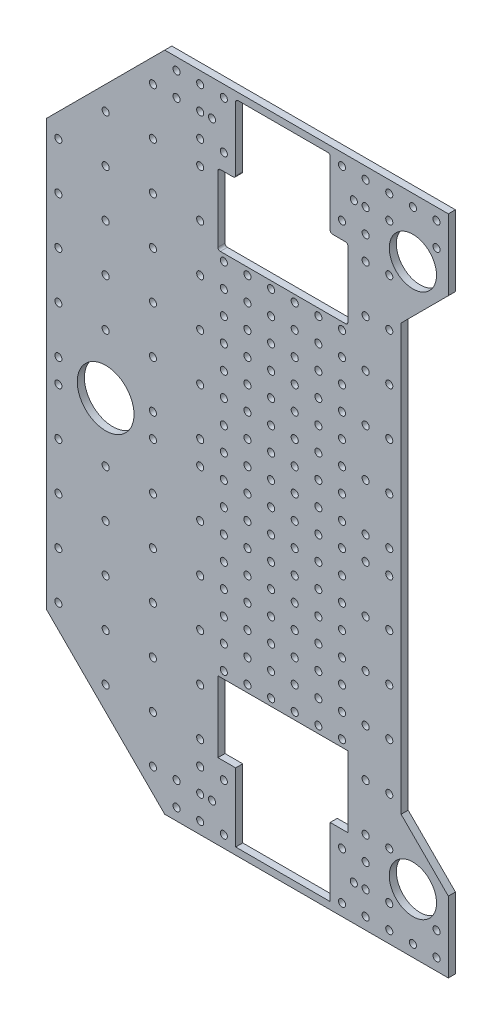
SolidWorks part; units mm, degrees
ref_plane "Front Plane" through (0, 0, 0) normal (0, 0, 1) x (1, 0, 0)
ref_plane "Top Plane" through (0, 0, 0) normal (0, 1, 0) x (1, 0, 0)
ref_plane "Right Plane" through (0, 0, 0) normal (1, 0, 0) x (0, 0, -1)
ref_axis "Axis1" through (-88.99, 0, 0) along (1, 0, 0)
ref_axis "Axis3" through (0, -55, 0) along (0, 1, 0)
sketch "Sketch1" plane through (0, 0, 0) normal (0, 0, 1) x (1, 0, 0)
  line L0 (-110, 90) -> (-110, -90)
  line L1 (-110, -90) -> (-60, -140)
  line L2 (-60, -140) -> (60, -140)
  line L3 (60, -140) -> (60, -110)
  line L4 (60, -110) -> (40, -90)
  line L5 (40, -90) -> (40, 90)
  line L6 (40, 90) -> (60, 110)
  line L7 (60, 110) -> (60, 140)
  line L8 (60, 140) -> (-60, 140)
  line L9 (-60, 140) -> (-110, 90)
  line L10 (-88.99, 0) -> (88.99, 0) construction
  circle A0 centre (78, 0) radius 38 construction
  circle A1 centre (78, -76) radius 38 construction
  circle A2 centre (78, 76) radius 38 construction
  point P2 (-110, 0)
  point P14 (-41.3479, 0)
  point P21 (0, 140)
  dimension "D15" = 76
  dimension "D1" = 180
  dimension "D2" = 170
  dimension "D3" = 50
  dimension "D4" = 50
  dimension "D5" = 135
  dimension "D6" = 110
  dimension "D7" = 20
  dimension "D8" = 180
  dimension "D9" = 120
  dimension "D10" = 28.2843
  dimension "D11" = 70.7107
  dimension "D12" = 50
  dimension "D13" = 30
  dimension "D14" = 30
  dimension "D16" = 120
  dimension "D17" = 280
extrude "Main" add sketch "Sketch1" along normal blind 3
sketch "Sketch2" plane through (0, 0, 3) normal (0, 0, 1) x (1, 0, 0)
  line L0 (-37.5, 108) -> (-37.5, 78)
  line L1 (-37.5, 78) -> (17.5, 78)
  line L2 (17.5, 78) -> (17.5, 108)
  line L3 (17.5, 108) -> (10, 108)
  line L4 (10, 108) -> (10, 137)
  line L5 (10, 137) -> (-30, 137)
  line L6 (-30, 137) -> (-30, 108)
  line L7 (-30, 108) -> (-37.5, 108)
  line L8 (0, -55) -> (0, 55) construction
  line L9 (-88.99, 0) -> (88.99, 0) construction
  line L10 (60, 140) -> (-60, 140) construction
  point P9 (-10, 78)
  dimension "D1" = 55
  dimension "D2" = 78
  dimension "D3" = 40
  dimension "D4" = 29
  dimension "D5" = 30
  dimension "D6" = 3
  dimension "D7" = 10
extrude "MotorCoderLeftHole" cut sketch "Sketch2" against normal through all
fillet "Fillet1" radius 1 8 edges at (-30, 137, 1.5) (10, 108, 1.5) (17.5, 108, 1.5) (10, 137, 1.5) (17.5, 78, 1.5) (-37.5, 78, 1.5) (-37.5, 108, 1.5) (-30, 108, 1.5)
sketch "Sketch7" plane through (0, 0, 3) normal (0, 0, 1) x (1, 0, 0)
  line L0 (-88.99, 0) -> (88.99, 0) construction
  line L1 (-15, 75) -> (-5, 75) construction
  line L2 (-36.5, 78) -> (16.5, 78) construction
  circle A0 centre (-15, 75) radius 1.5
  circle A1 centre (-25, 75) radius 1.5
  circle A2 centre (-5, 75) radius 1.5
  circle A3 centre (-35, 75) radius 1.5
  circle A4 centre (5, 75) radius 1.5
  circle A5 centre (15, 75) radius 1.5
  point P5 (-10, 78)
  point P6 (-10, 75)
  dimension "D1" = 3
  dimension "D2" = 75
  dimension "D3" = 10
  dimension "D4" = 10
  dimension "D5" = 10
  dimension "D6" = 10
  dimension "D7" = 10
extrude "MotorFixHoles" cut sketch "Sketch7" against normal through all
pattern_linear "MotorFixHoleLPattern" count 8 spacing 10 along (0, -1, 0) of "MotorFixHoles"
sketch "Sketch8" plane through (0, 0, 3) normal (0, 0, 1) x (1, 0, 0)
  line L0 (60, 140) -> (-60, 140) construction
  line L1 (-45, 135) -> (-35, 115) construction
  line L2 (-35, 135) -> (-45, 115) construction
  line L3 (0, -55) -> (0, 55) construction
  line L4 (-49, 135.7238) -> (-49, 114.2762) construction
  line L5 (-31, 114.2762) -> (-31, 135.7238) construction
  line L6 (-49, 125) -> (-31, 125) construction
  circle A0 centre (-40, 125) radius 1.5
  circle A1 centre (-45, 115) radius 1.5
  circle A2 centre (-35, 115) radius 1.5
  circle A3 centre (-45, 135) radius 1.5
  circle A4 centre (-35, 135) radius 1.5
  arc A5 (-49, 114.2762) -> (-31, 114.2762) centre (-40, 125) ccw construction
  arc A6 (-31, 135.7238) -> (-49, 135.7238) centre (-40, 125) ccw construction
  point P20 (-40, 125)
  point P24 (-40, 139)
  point P25 (-40, 111)
  dimension "D1" = 3
  dimension "D6" = 3
  dimension "D7" = 14
  dimension "D2" = 20
  dimension "D3" = 10
  dimension "D4" = 5
  dimension "D5" = 40
  dimension "D8" = 28
  dimension "D9" = 18
extrude "LinearBallFix" cut sketch "Sketch8" against normal through all
pattern_linear "LinearBallFix2" count 2 spacing 60 along (1, 0, 0) of "LinearBallFix"
sketch "Sketch4" plane through (0, 0, 3) normal (0, 0, 1) x (1, 0, 0)
  line L0 (-88.99, 0) -> (88.99, 0) construction
  circle A0 centre (-105, 5) radius 1.5
  dimension "D1" = 3
  dimension "D2" = 5
  dimension "D3" = 5
extrude "BottomLeftHole" cut sketch "Sketch4" against normal through all
pattern_linear "BottomLeftHoleLPattern" count 9 spacing 20 along (0, 1, 0) of "BottomLeftHole"
sketch "Sketch5" plane through (0, 0, 3) normal (0, 0, 1) x (1, 0, 0)
  line L1 (60, 110) -> (60, 140) construction
  circle A0 centre (-55, 135) radius 1.5
  circle A3 centre (35, 135) radius 1.5
  circle A4 centre (55, 135) radius 1.5
  dimension "D3" = 3
  dimension "D8" = 5
  dimension "D9" = 3
  dimension "D10" = 3
  dimension "D1" = 5
  dimension "D2" = 5
  dimension "D4" = 20
extrude "BottomLeftHole2" cut sketch "Sketch5" against normal through all
pattern_linear "BottomToTopPattern" count 4 spacing 20 along (1, 0, 0) of "BottomLeftHoleLPattern"
pattern_linear "LPattern3" count 2 spacing 10 along (0, -1, 0) of "BottomLeftHole2"
pattern_linear "FrontHoles" count 2 spacing 140 along (1, 0, 0) of "BottomLeftHoleLPattern"
sketch "Sketch9" plane through (0, 0, 3) normal (0, 0, 1) x (1, 0, 0)
  line L0 (-85, 5) -> (-85, 118.3839) construction
  line L1 (-65, 5) -> (-65, 125.7809) construction
  line L2 (-45, 5) -> (-45, 111.0784) construction
  line L3 (-105, 5) -> (-55, 135) construction
  line L4 (60, 140) -> (-60, 140) construction
  circle A0 centre (-85, 25) radius 1.5
  circle A1 centre (-65, 25) radius 1.5
  circle A2 centre (-45, 25) radius 1.5
  circle A3 centre (-65, 45) radius 1.5
  circle A4 centre (35, 105) radius 1.5
  circle A5 centre (35, 125) radius 1.5 construction
  circle A6 centre (45, 135) radius 1.5
  circle A7 centre (35, 135) radius 1.5 construction
  point P25 (35, 125)
  dimension "D1" = 3
  dimension "D4" = 20
  dimension "D5" = 10
  dimension "D2" = 20
  dimension "D3" = 20
  dimension "D6" = 5
extrude "Cut-Extrude2" cut sketch "Sketch9" against normal through all
pattern_linear "LPattern6" count 2 spacing 130 along (1, 0, 0) of "BottomLeftHoleLPattern"
mirror "Mirror1" about plane through (0, 0, 0) normal (0, 1, 0) of "LPattern6", "LPattern3", "FrontHoles", "MotorCoderLeftHole", "BottomLeftHole", "BottomLeftHoleLPattern", "BottomLeftHole2", "BottomToTopPattern", "MotorFixHoles", "MotorFixHoleLPattern", "LinearBallFix", "LinearBallFix2", "Cut-Extrude2"
sketch "Sketch3" plane through (0, 0, 3) normal (0, 0, 1) x (1, 0, 0)
  line L0 (-88.99, 0) -> (88.99, 0) construction
  line L1 (-110, 90) -> (-110, -90) construction
  line L3 (60, 110) -> (60, 140) construction
  line L5 (60, 140) -> (-60, 140) construction
  circle A0 centre (-85, 0) radius 12
  circle A1 centre (45, 115) radius 10
  circle A2 centre (45, -115) radius 10
  point P10 (45, 0)
  point P26 (45, 0)
  dimension "D1" = 24
  dimension "D3" = 20
  dimension "D6" = 230
  dimension "D2" = 25
  dimension "D4" = 15
  dimension "D5" = 25
extrude "BigHoles" cut sketch "Sketch3" against normal through all
